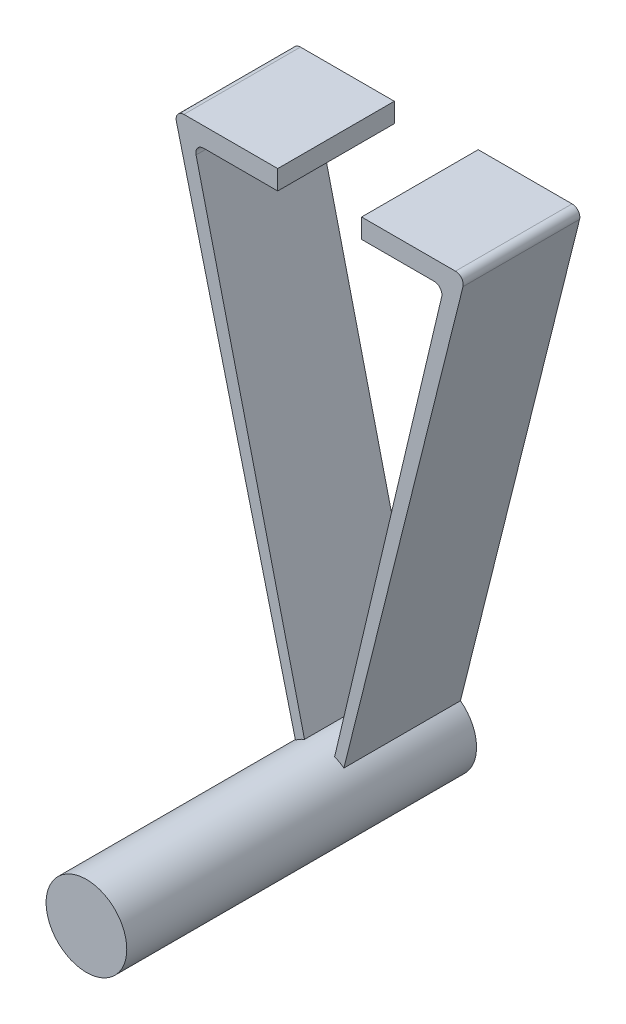
SolidWorks part; units mm, degrees
ref_plane "Front Plane" through (0, 0, 0) normal (0, 0, 1) x (1, 0, 0)
ref_plane "Top Plane" through (0, 0, 0) normal (0, 1, 0) x (1, 0, 0)
ref_plane "Right Plane" through (0, 0, 0) normal (1, 0, 0) x (0, 0, -1)
sketch "Sketch1" plane through (0, 0, 0) normal (0, 0, 1) x (1, 0, 0)
  line L0 (-37.5, 75) -> (0, -75)
  line L3 (-37.5, 75) -> (-10.7922, 75)
  line L5 (0, -75) -> (37.5, 75)
  line L6 (10.7922, 75) -> (37.5, 75)
  line L8 (-10.7922, 70) -> (-32.396, 70)
  line L9 (-32.396, 70) -> (-10.7922, 70)
  line L10 (0, -65) -> (-32.396, 70)
  line L11 (-32.396, 70) -> (-10.7922, 70)
  line L12 (31.9832, 70) -> (0, -65)
  line L14 (-10.7922, 70) -> (-10.7922, 75)
  line L16 (10.7922, 70) -> (10.7922, 75)
  line L19 (10.7922, 70) -> (31.9832, 70)
  line L20 (10.7922, 70) -> (31.9832, 70)
  point P0 (0, 0)
  point P2 (0, 72.5)
extrude "Boss-Extrude1" add sketch "Sketch1" along normal blind 30 contours L16 L19 L12 L10 L8 L14 L3 L0 L5 L6 region at (-24.1461, 73.3229, 0)
fillet "Fillet1" radius 2 6 edges at (0, -75, 15) (0, -65, 15) (37.5, 75, 15) (-37.5, 75, 15) (31.9832, 70, 15) (-32.396, 70, 15)
sketch "Sketch2" plane through (0, 0, 30) normal (0, 0, 1) x (1, 0, 0)
  circle A0 centre (-0.0096, -58.377) radius 10.3767
  arc A1 (-1.9573, -56.8437) -> (1.9337, -56.8381) centre (-0.0125, -56.377) ccw construction
extrude "Boss-Extrude2" add sketch "Sketch2" along normal mid plane 60
sketch "Sketch3" plane through (0, 0, 60) normal (0, 0, 1) x (1, 0, 0)
  circle A0 centre (-0.0096, -58.377) radius 10.3767
extrude "Boss-Extrude3" add sketch "Sketch3" along normal blind 30
